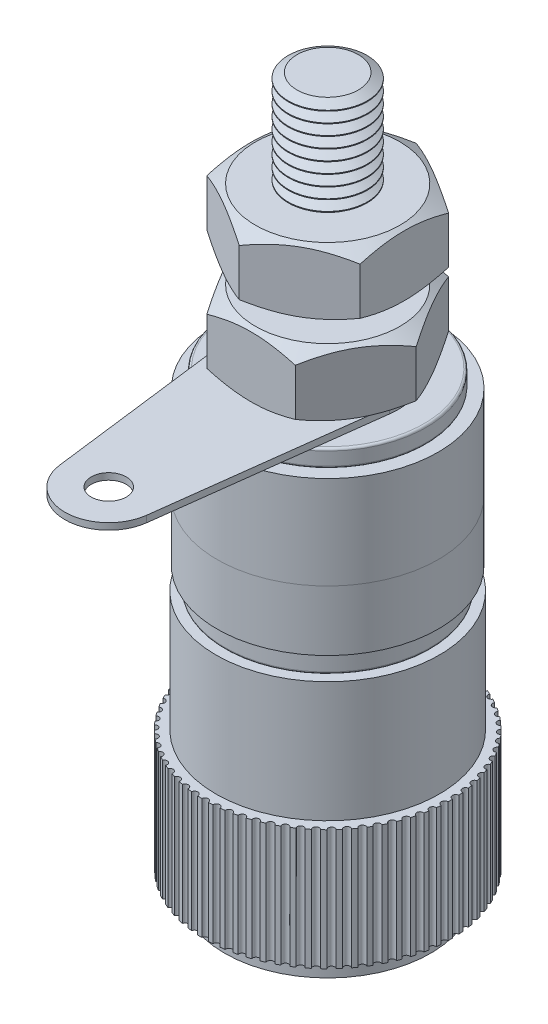
SolidWorks part; units mm, degrees
other "Plastic End"
other "Threaded Stud"
other "Plastic Ring 1"
other "Plastic Ring 2"
other "Washer"
other "Metal Tab"
other "Nut 1"
other "Nut 2"
ref_plane "Front Plane" through (0, 0, 0) normal (0, 0, 1) x (1, 0, 0)
ref_plane "Top Plane" through (0, 0, 0) normal (0, 1, 0) x (1, 0, 0)
ref_plane "Right Plane" through (0, 0, 0) normal (1, 0, 0) x (0, 0, -1)
sketch "Sketch1" plane through (0, 0, 0) normal (0, 1, 0) x (1, 0, 0)
  circle A0 centre (0, 0) radius 4.7
  circle A1 centre (0, 0) radius 3.1
  dimension "D1" = 9.4
  dimension "D2" = 6.2
extrude "Boss-Extrude1" add sketch "Sketch1" along normal blind 1
sketch "Sketch2" plane through (0, 1, 0) normal (0, 1, 0) x (1, 0, 0)
  circle A0 centre (0, 0) radius 5.6
  circle A1 centre (0, 0) radius 3.1 construction
  circle A2 centre (0, 0) radius 3.1
  dimension "D1" = 11.2
extrude "Boss-Extrude2" add sketch "Sketch2" along normal blind 3
sketch "Sketch4" plane through (0, 4, 0) normal (0, 1, 0) x (1, 0, 0)
  circle A0 centre (0, 0) radius 5.6 construction
  circle A1 centre (0, 0) radius 5.6
  circle A2 centre (0, 0) radius 2.25
  dimension "D1" = 4.5
extrude "Boss-Extrude3" add sketch "Sketch4" along normal blind 2.5
sketch "Sketch5" plane through (0, 6.5, 0) normal (0, 1, 0) x (1, 0, 0)
  circle A0 centre (0, 0) radius 5.1
  circle A1 centre (0, 0) radius 2.25 construction
  circle A2 centre (0, 0) radius 2.25
  dimension "D1" = 10.2
extrude "Boss-Extrude4" add sketch "Sketch5" along normal offset from surface (5.5 mm away) 12 up to face at (0, 0, 4.7)
sketch "Sketch6" plane through (0, 0, 0) normal (0, 0, 1) x (1, 0, 0)
  line L0 (0, 0) -> (0, 12) construction
  line L1 (5.1, 12) -> (-5.1, 12) construction
  line L2 (0, 12) -> (0, 32.5)
  line L3 (0, 12) -> (4.7, 12)
  line L4 (4.7, 12) -> (4.7, 13)
  line L5 (4.7, 13) -> (2.4, 13)
  line L6 (2.4, 13) -> (2.4, 16.75)
  line L7 (2.4, 16.75) -> (1.8, 16.75)
  line L8 (1.8, 16.75) -> (1.8, 32.5)
  line L9 (1.8, 32.5) -> (0, 32.5)
  dimension "D1" = 20.5
  dimension "D2" = 4.7
  dimension "D3" = 1
  dimension "D4" = 2.4
  dimension "D5" = 3.75
  dimension "D6" = 1.8
revolve "Revolve1" add sketch "Sketch6" angle 360 about L0
sketch "Sketch7" plane through (0, 0, 0) normal (0, 0, 1) x (1, 0, 0)
  line L0 (0, 0) -> (0, 12) construction
  line L1 (-3.1, 0) -> (3.1, 0) construction
  line L2 (2.25, 12) -> (-2.25, 12) construction
  line L3 (0, 12) -> (0, 14)
  line L4 (0, 14) -> (0.55, 14)
  line L5 (0, 12) -> (2.05, 12)
  line L6 (-4.7, 12) -> (4.7, 12) construction
  line L9 (5.1, 12) -> (-5.1, 12) construction
  line L10 (2.05, 12) -> (2.05, 12.5)
  arc A1 (2.05, 12.5) -> (0.55, 14) centre (0.55, 12.5) ccw
  dimension "D1" = 2.05
  dimension "D2" = 14
  dimension "D3" = 0.5
revolve "Cut-Revolve1" cut sketch "Sketch7" angle 360 about L0
sketch "Sketch8" plane through (0, 0, 0) normal (0, 0, 1) x (1, 0, 0)
  line L0 (0, 0) -> (0, 32.5) construction
  line L1 (1.8, 32.5) -> (-1.8, 32.5) construction
  line L2 (0, 32.5) -> (1.4, 32.5) construction
  line L3 (1.4, 32.5) -> (1.833, 32.5) construction
  line L4 (1.833, 32.5) -> (2.333, 32.5) construction
  line L5 (1.833, 32.75) -> (1.833, 32.25) construction
  line L6 (2.333, 32.75) -> (2.333, 32.25)
  line L7 (2.333, 32.75) -> (1.833, 32.75)
  line L8 (1.833, 32.75) -> (1.4, 32.5)
  line L9 (1.4, 32.5) -> (1.833, 32.25)
  line L10 (1.833, 32.25) -> (2.333, 32.25)
  dimension "D1" = 60
  dimension "D2" = 0.5
  dimension "D3" = 1.4
revolve "Cut-Revolve2" cut sketch "Sketch8" angle 360 about L0
pattern_linear "LPattern1" count 30 spacing 0.5 along (0, -1, 0) of "Cut-Revolve2"
sketch "Sketch9" plane through (0, 0, 0) normal (0, 0, 1) x (1, 0, 0)
  line L0 (0, 0) -> (0, 13) construction
  line L1 (4.7, 13) -> (-4.7, 13) construction
  line L2 (0, 13) -> (0, 18.25) construction
  line L3 (2.5, 18.25) -> (4, 18.25)
  line L4 (4, 18.25) -> (4, 15.75)
  line L5 (4, 15.75) -> (5.05, 15.75)
  line L6 (5.05, 15.75) -> (5.05, 13)
  line L7 (5.05, 13) -> (2.5, 13)
  line L8 (2.5, 18.25) -> (2.5, 13)
  line L9 (0, 18.25) -> (2.5, 18.25) construction
  line L10 (0, 13) -> (2.5, 13) construction
  dimension "D1" = 5.25
  dimension "D2" = 2.75
  dimension "D3" = 5.05
  dimension "D4" = 4
  dimension "D5" = 2.5
revolve "Revolve2" add sketch "Sketch9" angle 360 about L2
sketch "Sketch11" plane through (0, 0, 0) normal (0, 0, 1) x (1, 0, 0)
  line L0 (0, 0) -> (0, 13) construction
  line L1 (4.7, 13) -> (-4.7, 13) construction
  line L2 (0, 13) -> (0, 15.75) construction
  line L3 (5.05, 15.75) -> (-5.05, 15.75) construction
  line L4 (0, 15.75) -> (0, 18.35) construction
  line L6 (2, 18.35) -> (4.1, 18.35)
  line L7 (4.1, 18.35) -> (4.1, 15.75)
  line L8 (4.1, 15.75) -> (5.05, 15.75)
  line L9 (2, 20) -> (5.05, 20)
  line L10 (5.05, 20) -> (5.05, 15.75)
  line L11 (2, 20) -> (2, 18.35)
  line L12 (2, 18.35) -> (0, 18.35) construction
  line L13 (0, 18.35) -> (0, 20) construction
  line L14 (0, 20) -> (2, 20) construction
  dimension "D1" = 7
  dimension "D2" = 2.6
  dimension "D3" = 4.1
  dimension "D4" = 2
revolve "Revolve4" add sketch "Sketch11" angle 360 about L13
sketch "Sketch12" plane through (0, 20, 0) normal (0, 1, 0) x (1, 0, 0)
  circle A0 centre (0, 0) radius 4.5
  circle A1 centre (0, 0) radius 2.2
  dimension "D1" = 9
  dimension "D2" = 4.4
extrude "Boss-Extrude5" add sketch "Sketch12" along normal blind 0.8 separate body
sketch "Sketch13" plane through (0, 12, 0) normal (0, -1, 0) x (1, 0, 0)
  circle A0 centre (0, 0) radius 2.25 construction
  circle A1 centre (0, 0) radius 2.25
  circle A2 centre (0, 0) radius 2.05 construction
  circle A3 centre (0, 0) radius 2.05
extrude "Boss-Extrude6" add sketch "Sketch13" along normal up to surface (8 mm away) up to face at (0, 4, 2.25)
fillet "Fillet1" radius 0.1 2 edges at (0, 4, 2.25) (0, 4, 2.05)
fillet "Fillet2" radius 0.1 2 edges at (0, 12, -4.7) (0, 13, -4.7)
fillet "Fillet3" radius 0.1 2 edges at (0, 20, 4.5) (0, 20.8, 4.5)
sketch "Sketch14" plane through (0, 20.8, 0) normal (0, 1, 0) x (1, 0, 0)
  line L0 (0, 0) -> (0, -10) construction
  line L1 (-3.25, 0) -> (3.25, 0) construction
  line L3 (-3.2245, -0.4062) -> (-1.9843, -10.25)
  line L4 (3.2245, -0.4062) -> (1.9843, -10.25)
  arc A0 (3.2245, -0.4062) -> (-3.2245, -0.4062) centre (0, 0) ccw
  arc A1 (-1.9843, -10.25) -> (1.9843, -10.25) centre (0, -10) ccw
  circle A2 centre (0, 0) radius 2.1
  circle A3 centre (0, -10) radius 0.8
  dimension "D1" = 3.25
  dimension "D2" = 10
  dimension "D3" = 2
  dimension "D4" = 4.2
  dimension "D5" = 1.6
extrude "Boss-Extrude7" add sketch "Sketch14" along normal blind 0.3 separate body
sketch "Sketch15" plane through (0, 21.1, 0) normal (0, 1, 0) x (1, 0, 0)
  line L1 (4.0415, 0) -> (2.0207, 3.5)
  line L2 (2.0207, 3.5) -> (-2.0207, 3.5)
  line L3 (-2.0207, 3.5) -> (-4.0415, 0)
  line L4 (-4.0415, 0) -> (-2.0207, -3.5)
  line L5 (-2.0207, -3.5) -> (2.0207, -3.5)
  line L6 (2.0207, -3.5) -> (4.0415, 0)
  circle A0 centre (0, 0) radius 3.5 construction
  circle A1 centre (0, 0) radius 1.625
  dimension "D1" = 7
  dimension "D2" = 3.25
extrude "Boss-Extrude8" add sketch "Sketch15" along normal blind 3 separate body
sketch "Sketch16" plane through (0, 0, 0) normal (0, 0, 1) x (1, 0, 0)
  line L0 (0, 0) -> (0, 21.1) construction
  line L1 (-2.0207, 21.1) -> (2.0207, 21.1) construction
  line L2 (0, 21.1) -> (0, 24.1) construction
  line L3 (-2.0207, 24.1) -> (2.0207, 24.1) construction
  line L4 (0, 24.1) -> (3.3, 24.1) construction
  line L5 (2.0207, 24.1) -> (4.0415, 24.1) construction
  line L6 (3.3, 24.1) -> (3.3, 21.1) construction
  line L7 (2.0207, 21.1) -> (4.0415, 21.1) construction
  line L8 (3.3, 21.1) -> (0, 21.1) construction
  line L9 (3.3, 24.1) -> (4.0415, 24.1)
  line L10 (4.0415, 24.1) -> (4.0415, 23.6719)
  line L11 (4.0415, 24.1) -> (4.0415, 21.1) construction
  line L12 (4.0415, 23.6719) -> (3.3, 24.1)
  line L13 (3.3, 21.1) -> (4.0415, 21.1)
  line L14 (4.0415, 21.1) -> (4.0415, 21.5281)
  line L15 (4.0415, 21.5281) -> (3.3, 21.1)
  dimension "D1" = 30
  dimension "D2" = 3.3
revolve "Cut-Revolve3" cut sketch "Sketch16" angle 360 about L2
ref_plane "Plane NUT GAP" through (0, 25.1, 0) normal (0, 1, 0) x (1, 0, 0)
sketch "Sketch17" plane through (0, 25.1, 0) normal (0, 1, 0) x (1, 0, 0)
  line L1 (3.5, -2.0207) -> (3.5, 2.0207)
  line L2 (3.5, 2.0207) -> (0, 4.0415)
  line L3 (0, 4.0415) -> (-3.5, 2.0207)
  line L4 (-3.5, 2.0207) -> (-3.5, -2.0207)
  line L5 (-3.5, -2.0207) -> (0, -4.0415)
  line L6 (0, -4.0415) -> (3.5, -2.0207)
  circle A0 centre (0, 0) radius 3.5 construction
  circle A1 centre (0, 0) radius 1.625
  dimension "D1" = 7
  dimension "D2" = 3.25
extrude "Boss-Extrude9" add sketch "Sketch17" along normal blind 3 separate body
sketch "Sketch18" plane through (0, 0, 0) normal (1, 0, 0) x (0, 0, -1)
  line L0 (0, 0) -> (0, 25.1) construction
  line L1 (-2.0207, 25.1) -> (2.0207, 25.1) construction
  line L2 (0, 25.1) -> (0, 28.1) construction
  line L3 (-2.0207, 28.1) -> (2.0207, 28.1) construction
  line L4 (0, 28.1) -> (3.3, 28.1) construction
  line L5 (2.0207, 28.1) -> (4.0415, 28.1) construction
  line L6 (3.3, 28.1) -> (3.3, 25.1) construction
  line L7 (2.0207, 25.1) -> (4.0415, 25.1) construction
  line L8 (3.3, 25.1) -> (0, 25.1) construction
  line L9 (3.3, 28.1) -> (4.0415, 28.1)
  line L10 (4.0415, 28.1) -> (4.0415, 25.1) construction
  line L11 (4.0415, 28.1) -> (4.0415, 27.6719)
  line L12 (4.0415, 27.6719) -> (3.3, 28.1)
  line L13 (3.3, 25.1) -> (4.0415, 25.1)
  line L14 (4.0415, 25.1) -> (4.0415, 25.5281)
  line L15 (4.0415, 25.5281) -> (3.3, 25.1)
  dimension "D1" = 3.3
  dimension "D2" = 30
revolve "Cut-Revolve4" cut sketch "Sketch18" angle 360 about L2
sketch "Sketch19" plane through (0, 1, 0) normal (0, -1, 0) x (1, 0, 0)
  line L0 (0, 0) -> (0, -5.6) construction
  circle A0 centre (0, 0) radius 5.6 construction
  circle A1 centre (0, -5.6) radius 0.15
  dimension "D1" = 0.3
extrude "Cut-Extrude1" cut sketch "Sketch19" against normal up to surface (5.5 mm away) up to face at (0, 6.5, 5.1)
pattern_circular "CirPattern1" count 70 over 360 about axis through (0, 4, 0) along (0, -1, 0) of "Cut-Extrude1"
